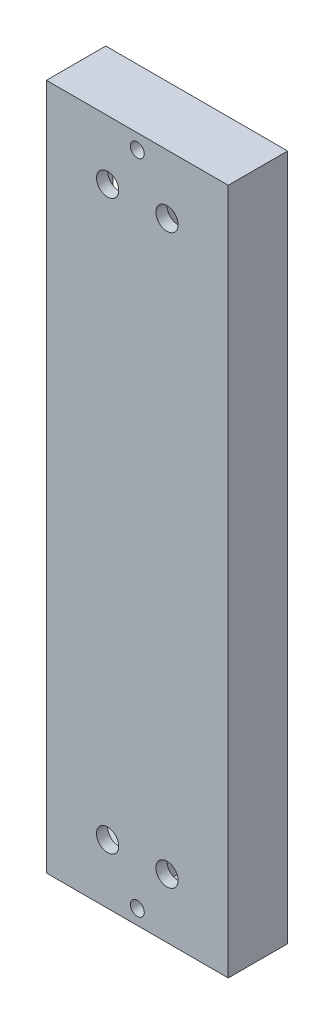
SolidWorks part; units mm, degrees
ref_plane "Front Plane" through (0, 0, 0) normal (0, 0, 1) x (1, 0, 0)
ref_plane "Top Plane" through (0, 0, 0) normal (0, 1, 0) x (1, 0, 0)
ref_plane "Right Plane" through (0, 0, 0) normal (1, 0, 0) x (0, 0, -1)
sketch "Sketch1" plane through (0, 0, 0) normal (0, 0, 1) x (1, 0, 0)
  line L0 (-6.5, 84.5) -> (6.5, 84.5) construction
  line L1 (-6.5, -84.5) -> (6.5, -84.5)
  line L2 (-6.5, -84.5) -> (-6.5, 84.5)
  line L3 (-6.5, 84.5) -> (6.5, 84.5)
  line L4 (6.5, -84.5) -> (6.5, 84.5)
  line L5 (6.5, -84.5) -> (6.5, 84.5) construction
  line L6 (6.5, -84.5) -> (9.5, 84.5) construction
  line L7 (9.5, -84.5) -> (22.5, -84.5)
  line L8 (9.5, -84.5) -> (9.5, 84.5)
  line L9 (9.5, 84.5) -> (22.5, 84.5)
  line L10 (22.5, -84.5) -> (22.5, 84.5)
  line L11 (-16.5, -84.5) -> (32.5, -84.5)
  line L12 (-16.5, -92.5) -> (32.5, -92.5)
  line L13 (-16.5, -92.5) -> (-16.5, 92.5)
  line L14 (-16.5, 92.5) -> (32.5, 92.5)
  line L15 (32.5, -92.5) -> (32.5, 92.5)
  line L16 (-16.5, -92.5) -> (32.5, 92.5) construction
  line L17 (-16.5, 92.5) -> (32.5, -92.5) construction
  line L18 (-16.5, 84.5) -> (32.5, 84.5)
  line L19 (-14.5, -84.5) -> (-14.5, 84.5)
  line L20 (30.5, -84.5) -> (30.5, 84.5)
  line L21 (8, -92.5) -> (8, -84.5) construction
  line L22 (32.5, 0) -> (-16.5, 0) construction
  circle A0 centre (0, -76.5) radius 3
  circle A1 centre (16, -76.5) radius 3
  circle A2 centre (0, 76.5) radius 3
  circle A3 centre (16, 76.5) radius 3
  circle A4 centre (8, -88.5) radius 1.875
  circle A5 centre (8, 88.5) radius 1.875
  point P26 (8, 0)
  dimension "D3" = 3.75
  dimension "D1" = 10
  dimension "D2" = 8
  dimension "D4" = 2
  dimension "D5" = 2
extrude "Boss-Extrude1" add sketch "Sketch1" along normal blind 3 contours A2 | A3 | A0 | A1 | L13 L14 L15 L12 | A5 | A4 region at (0, -76.5, 0) region at (16, -76.5, 0) region at (0, 76.5, 0) region at (16, 76.5, 0)
extrude "Boss-Extrude2" add sketch "Sketch1<3>" against normal up to surface (13 mm away) contours L13 L18 L3 L9 L15 L14 A5 | L11 L19 L18 L13 | L12 L15 L11 L7 L1 L13 A4 | L20 L11 L15 L18 | L18 L4 L11 L8 region at (0, -84.9965, 0) region at (8, 0, 0) region at (-10.5, 84.9965, 0) region at (-15.5, 0, 0) region at (31.5, 0, 0)
sketch "Sketch1<3>" plane through (0, 0, 0) normal (0, 0, 1) x (1, 0, 0) same geometry as "Sketch1"
equation "\"D5@Sketch1\"=\"D4@Sketch1\""
